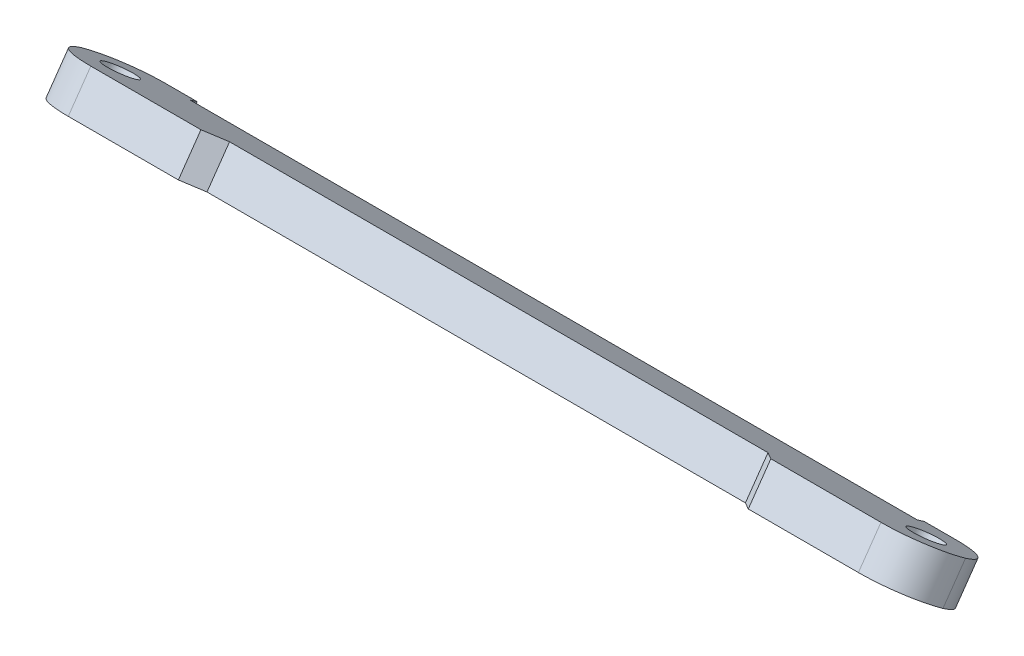
SolidWorks part; units mm, degrees
material "PET"
ref_plane "Front Plane" through (0, 0, 0) normal (0, 0, 1) x (1, 0, 0)
ref_plane "Top Plane" through (0, 0, 0) normal (0, 1, 0) x (1, 0, 0)
ref_plane "Right Plane" through (0, 0, 0) normal (1, 0, 0) x (0, 0, -1)
sketch "Sketch1" plane through (0, -2.867, 2.0075) normal (0, -0.8192, 0.5736) x (1, 0, 0)
  line L7 (-51.2273, -89.0944) -> (-56.2273, -89.0944) construction
  line L12 (-56.2273, -83.2909) -> (-56.2273, -94.8979)
  line L13 (-56.2273, -94.8979) -> (-46.2273, -94.8979)
  line L14 (-46.2273, -94.8979) -> (-46.2273, -93.794)
  line L15 (-46.2273, -93.794) -> (-36.2273, -93.794)
  line L16 (-36.2273, -93.794) -> (-36.2273, -83.2909)
  line L17 (-36.2273, -83.2909) -> (-56.2273, -83.2909)
  line L18 (-56.2273, -83.2909) -> (-56.2273, -94.8979)
  line L19 (-56.2273, -94.8979) -> (-46.2273, -94.8979)
  line L21 (-46.2273, -93.794) -> (-36.2273, -93.794)
  line L22 (-36.2273, -93.794) -> (-36.2273, -83.2909)
  line L23 (-36.2273, -83.2909) -> (-56.2273, -83.2909)
  line L50 (-36.2273, -93.794) -> (36.2273, -93.794) construction
  line L51 (0, -93.794) -> (0, -63.8424) construction
  line L52 (36.2273, -83.2909) -> (56.2273, -83.2909)
  line L53 (36.2273, -93.794) -> (36.2273, -83.2909)
  line L54 (46.2273, -93.794) -> (36.2273, -93.794)
  line L55 (46.2273, -94.8979) -> (46.2273, -93.794)
  line L56 (56.2273, -94.8979) -> (46.2273, -94.8979)
  line L57 (56.2273, -83.2909) -> (56.2273, -94.8979)
  line L135 (-46.2273, -94.8979) -> (-46.2273, -93.794)
  circle A0 centre (-51.2273, -89.0944) radius 2
  circle A3 centre (51.2273, -89.0944) radius 2
  dimension "D3" = 4
  dimension "D2" = 0
  dimension "D1" = 0
extrude "Boss-Extrude1" add sketch "Sketch1" along normal blind 5
sketch "Sketch2" plane through (0, -6.9628, 4.8754) normal (0, -0.8192, 0.5736) x (1, 0, 0)
  line L0 (36.2273, -83.2909) -> (36.2273, -93.794) construction
  line L1 (-36.2273, -93.794) -> (36.2273, -93.794)
  line L2 (-36.2273, -93.794) -> (-36.2273, -85.2909)
  line L3 (-36.2273, -85.2909) -> (36.2273, -85.2909)
  line L4 (36.2273, -93.794) -> (36.2273, -85.2909)
  line L5 (56.2273, -83.2909) -> (36.2273, -83.2909) construction
  dimension "D1" = 2
extrude "Boss-Extrude2" add sketch "Sketch2" against normal blind 5
chamfer "Chamfer1" distance 2 angle 45 2 edges at (36.2273, -53.8358, -66.4248) (-36.2273, -53.8358, -66.4248)
fillet "Fillet1" radius 6 4 edges at (56.2273, -59.3461, -74.2943) (56.2273, -52.6886, -64.7865) (-56.2273, -52.6886, -64.7865) (-56.2273, -59.3461, -74.2943)
